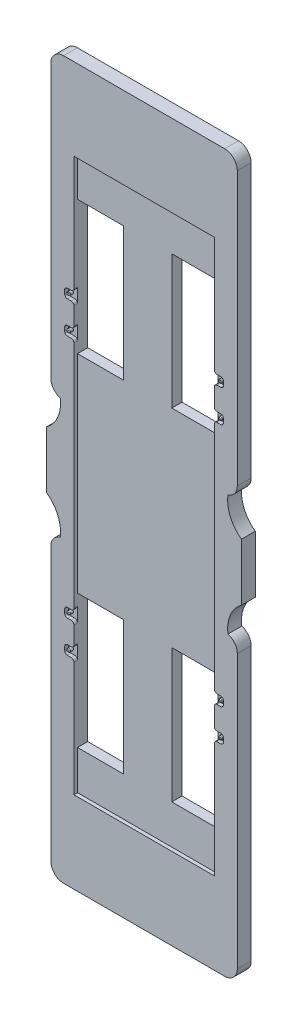
SolidWorks part; units mm, degrees
ref_plane "Front Plane" through (0, 0, 0) normal (0, 0, 1) x (1, 0, 0)
ref_plane "Top Plane" through (0, 0, 0) normal (0, 1, 0) x (1, 0, 0)
ref_plane "Right Plane" through (0, 0, 0) normal (1, 0, 0) x (0, 0, -1)
sketch "Sketch1" plane through (0, 0, 0.1) normal (0, 0, 1) x (1, 0, 0)
  line L12 (40.45, 31.4857) -> (40.45, 150)
  line L14 (40.45, 31.4857) -> (40.45, 150)
  line L16 (-40.45, -31.4857) -> (-40.45, -150)
  line L17 (-34.95, -155.5) -> (34.95, -155.5)
  line L18 (40.45, -150) -> (40.45, -31.4857)
  line L19 (42.25, -12.4178) -> (42.25, 12.4178)
  line L24 (-40.45, -31.4857) -> (-40.45, -150)
  line L25 (-34.95, -155.5) -> (34.95, -155.5)
  line L26 (40.45, -150) -> (40.45, -31.4857)
  line L27 (42.25, -12.4178) -> (42.25, 12.4178)
  line L38 (34.95, 155.5) -> (-34.95, 155.5)
  line L39 (34.95, 155.5) -> (-34.95, 155.5)
  line L40 (-40.45, 150) -> (-40.45, 31.4857)
  line L41 (-40.45, 150) -> (-40.45, 31.4857)
  line L42 (-42.25, 12.4178) -> (-42.25, -12.4178)
  line L43 (-42.25, 12.4178) -> (-42.25, -12.4178)
  line L48 (-30.45, 120) -> (-30.45, 70.2)
  line L49 (-31.65, 69) -> (-33.25, 69)
  line L50 (-34.45, 67.8) -> (-34.45, 66.2)
  line L51 (-33.25, 65) -> (-31.65, 65)
  line L52 (-30.45, 63.8) -> (-30.45, 56.2)
  line L53 (-31.65, 55) -> (-33.25, 55)
  line L54 (-34.45, 53.8) -> (-34.45, 52.2)
  line L55 (-33.25, 51) -> (-31.65, 51)
  line L56 (-30.45, 49.8) -> (-30.45, 0)
  line L57 (-30.45, 0) -> (30.45, 0)
  line L58 (30.45, 0) -> (30.45, 49.8)
  line L59 (31.65, 51) -> (33.25, 51)
  line L60 (34.45, 52.2) -> (34.45, 53.8)
  line L61 (33.25, 55) -> (31.65, 55)
  line L62 (30.45, 56.2) -> (30.45, 63.8)
  line L63 (31.65, 65) -> (33.25, 65)
  line L64 (34.45, 66.2) -> (34.45, 67.8)
  line L65 (33.25, 69) -> (31.65, 69)
  line L66 (30.45, 70.2) -> (30.45, 120)
  line L67 (30.45, 120) -> (-30.45, 120)
  line L68 (-30.45, 120) -> (-30.45, 70.2)
  line L69 (-31.65, 69) -> (-33.25, 69)
  line L70 (-34.45, 67.8) -> (-34.45, 66.2)
  line L71 (-33.25, 65) -> (-31.65, 65)
  line L72 (-30.45, 63.8) -> (-30.45, 56.2)
  line L73 (-31.65, 55) -> (-33.25, 55)
  line L74 (-34.45, 53.8) -> (-34.45, 52.2)
  line L75 (-33.25, 51) -> (-31.65, 51)
  line L76 (-30.45, 49.8) -> (-30.45, 0)
  line L77 (-30.45, 0) -> (30.45, 0)
  line L78 (30.45, 0) -> (30.45, 49.8)
  line L79 (31.65, 51) -> (33.25, 51)
  line L80 (34.45, 52.2) -> (34.45, 53.8)
  line L81 (33.25, 55) -> (31.65, 55)
  line L82 (30.45, 56.2) -> (30.45, 63.8)
  line L83 (31.65, 65) -> (33.25, 65)
  line L84 (34.45, 66.2) -> (34.45, 67.8)
  line L85 (33.25, 69) -> (31.65, 69)
  line L86 (30.45, 70.2) -> (30.45, 120)
  line L87 (30.45, 120) -> (-30.45, 120)
  line L88 (-30.45, 0) -> (-30.45, -49.8)
  line L89 (-31.65, -51) -> (-33.25, -51)
  line L90 (-34.45, -52.2) -> (-34.45, -53.8)
  line L91 (-33.25, -55) -> (-31.65, -55)
  line L92 (-30.45, -56.2) -> (-30.45, -63.8)
  line L93 (-31.65, -65) -> (-33.25, -65)
  line L94 (-34.45, -66.2) -> (-34.45, -67.8)
  line L95 (-33.25, -69) -> (-31.65, -69)
  line L96 (-30.45, -70.2) -> (-30.45, -120)
  line L97 (-30.45, -120) -> (30.45, -120)
  line L98 (30.45, -120) -> (30.45, -70.2)
  line L99 (31.65, -69) -> (33.25, -69)
  line L100 (34.45, -67.8) -> (34.45, -66.2)
  line L101 (33.25, -65) -> (31.65, -65)
  line L102 (30.45, -63.8) -> (30.45, -56.2)
  line L103 (31.65, -55) -> (33.25, -55)
  line L104 (34.45, -53.8) -> (34.45, -52.2)
  line L105 (33.25, -51) -> (31.65, -51)
  line L106 (30.45, -49.8) -> (30.45, 0)
  line L107 (30.45, 0) -> (-30.45, 0)
  line L108 (-30.45, 0) -> (-30.45, -49.8)
  line L109 (-31.65, -51) -> (-33.25, -51)
  line L110 (-34.45, -52.2) -> (-34.45, -53.8)
  line L111 (-33.25, -55) -> (-31.65, -55)
  line L112 (-30.45, -56.2) -> (-30.45, -63.8)
  line L113 (-31.65, -65) -> (-33.25, -65)
  line L114 (-34.45, -66.2) -> (-34.45, -67.8)
  line L115 (-33.25, -69) -> (-31.65, -69)
  line L116 (-30.45, -70.2) -> (-30.45, -120)
  line L117 (-30.45, -120) -> (30.45, -120)
  line L118 (30.45, -120) -> (30.45, -70.2)
  line L119 (31.65, -69) -> (33.25, -69)
  line L120 (34.45, -67.8) -> (34.45, -66.2)
  line L121 (33.25, -65) -> (31.65, -65)
  line L122 (30.45, -63.8) -> (30.45, -56.2)
  line L123 (31.65, -55) -> (33.25, -55)
  line L124 (34.45, -53.8) -> (34.45, -52.2)
  line L125 (33.25, -51) -> (31.65, -51)
  line L126 (30.45, -49.8) -> (30.45, 0)
  line L127 (30.45, 0) -> (-30.45, 0)
  circle A0 centre (-32.95, -67) radius 0.75 construction
  circle A1 centre (-32.95, -53) radius 0.75 construction
  circle A2 centre (32.95, -67) radius 0.75 construction
  circle A3 centre (32.95, -53) radius 0.75 construction
  circle A4 centre (32.95, 53) radius 0.75 construction
  circle A5 centre (32.95, 67) radius 0.75 construction
  circle A6 centre (-32.95, 53) radius 0.75 construction
  circle A7 centre (-32.95, 67) radius 0.75 construction
  circle A16 centre (-32.95, -67) radius 0.75
  circle A17 centre (-32.95, -53) radius 0.75
  circle A18 centre (32.95, -67) radius 0.75
  circle A19 centre (32.95, -53) radius 0.75
  circle A20 centre (32.95, 53) radius 0.75
  circle A21 centre (32.95, 67) radius 0.75
  circle A22 centre (-32.95, 53) radius 0.75
  circle A23 centre (-32.95, 67) radius 0.75
  arc A32 (-36.3903, -26.1776) -> (-42.25, -12.4178) centre (-50.75, -24.1652) ccw
  arc A33 (-36.3903, -26.1776) -> (-40.45, -31.4857) centre (-34.95, -31.4857) ccw
  arc A34 (-40.45, -150) -> (-34.95, -155.5) centre (-34.95, -150) ccw
  arc A35 (34.95, -155.5) -> (40.45, -150) centre (34.95, -150) ccw
  arc A36 (40.45, -31.4857) -> (36.3903, -26.1776) centre (34.95, -31.4857) ccw
  arc A37 (42.25, -12.4178) -> (36.3903, -26.1776) centre (50.75, -24.1652) ccw
  arc A44 (-36.3903, -26.1776) -> (-42.25, -12.4178) centre (-50.75, -24.1652) ccw
  arc A45 (-36.3903, -26.1776) -> (-40.45, -31.4857) centre (-34.95, -31.4857) ccw
  arc A46 (-40.45, -150) -> (-34.95, -155.5) centre (-34.95, -150) ccw
  arc A47 (34.95, -155.5) -> (40.45, -150) centre (34.95, -150) ccw
  arc A48 (40.45, -31.4857) -> (36.3903, -26.1776) centre (34.95, -31.4857) ccw
  arc A49 (42.25, -12.4178) -> (36.3903, -26.1776) centre (50.75, -24.1652) ccw
  arc A56 (-31.65, 69) -> (-30.45, 70.2) centre (-31.65, 70.2) ccw
  arc A57 (-33.25, 69) -> (-34.45, 67.8) centre (-33.25, 67.8) ccw
  arc A58 (-34.45, 66.2) -> (-33.25, 65) centre (-33.25, 66.2) ccw
  arc A59 (-30.45, 63.8) -> (-31.65, 65) centre (-31.65, 63.8) ccw
  arc A60 (-31.65, 55) -> (-30.45, 56.2) centre (-31.65, 56.2) ccw
  arc A61 (-33.25, 55) -> (-34.45, 53.8) centre (-33.25, 53.8) ccw
  arc A62 (-34.45, 52.2) -> (-33.25, 51) centre (-33.25, 52.2) ccw
  arc A63 (-30.45, 49.8) -> (-31.65, 51) centre (-31.65, 49.8) ccw
  arc A64 (31.65, 51) -> (30.45, 49.8) centre (31.65, 49.8) ccw
  arc A65 (33.25, 51) -> (34.45, 52.2) centre (33.25, 52.2) ccw
  arc A66 (34.45, 53.8) -> (33.25, 55) centre (33.25, 53.8) ccw
  arc A67 (30.45, 56.2) -> (31.65, 55) centre (31.65, 56.2) ccw
  arc A68 (31.65, 65) -> (30.45, 63.8) centre (31.65, 63.8) ccw
  arc A69 (33.25, 65) -> (34.45, 66.2) centre (33.25, 66.2) ccw
  arc A70 (34.45, 67.8) -> (33.25, 69) centre (33.25, 67.8) ccw
  arc A71 (30.45, 70.2) -> (31.65, 69) centre (31.65, 70.2) ccw
  arc A72 (-31.65, 69) -> (-30.45, 70.2) centre (-31.65, 70.2) ccw
  arc A73 (-33.25, 69) -> (-34.45, 67.8) centre (-33.25, 67.8) ccw
  arc A74 (-34.45, 66.2) -> (-33.25, 65) centre (-33.25, 66.2) ccw
  arc A75 (-30.45, 63.8) -> (-31.65, 65) centre (-31.65, 63.8) ccw
  arc A76 (-31.65, 55) -> (-30.45, 56.2) centre (-31.65, 56.2) ccw
  arc A77 (-33.25, 55) -> (-34.45, 53.8) centre (-33.25, 53.8) ccw
  arc A78 (-34.45, 52.2) -> (-33.25, 51) centre (-33.25, 52.2) ccw
  arc A79 (-30.45, 49.8) -> (-31.65, 51) centre (-31.65, 49.8) ccw
  arc A80 (31.65, 51) -> (30.45, 49.8) centre (31.65, 49.8) ccw
  arc A81 (33.25, 51) -> (34.45, 52.2) centre (33.25, 52.2) ccw
  arc A82 (34.45, 53.8) -> (33.25, 55) centre (33.25, 53.8) ccw
  arc A83 (30.45, 56.2) -> (31.65, 55) centre (31.65, 56.2) ccw
  arc A84 (31.65, 65) -> (30.45, 63.8) centre (31.65, 63.8) ccw
  arc A85 (33.25, 65) -> (34.45, 66.2) centre (33.25, 66.2) ccw
  arc A86 (34.45, 67.8) -> (33.25, 69) centre (33.25, 67.8) ccw
  arc A87 (30.45, 70.2) -> (31.65, 69) centre (31.65, 70.2) ccw
  arc A100 (-31.65, -51) -> (-30.45, -49.8) centre (-31.65, -49.8) ccw
  arc A101 (-33.25, -51) -> (-34.45, -52.2) centre (-33.25, -52.2) ccw
  arc A102 (-34.45, -53.8) -> (-33.25, -55) centre (-33.25, -53.8) ccw
  arc A103 (-30.45, -56.2) -> (-31.65, -55) centre (-31.65, -56.2) ccw
  arc A104 (-31.65, -65) -> (-30.45, -63.8) centre (-31.65, -63.8) ccw
  arc A105 (-33.25, -65) -> (-34.45, -66.2) centre (-33.25, -66.2) ccw
  arc A106 (-34.45, -67.8) -> (-33.25, -69) centre (-33.25, -67.8) ccw
  arc A107 (-30.45, -70.2) -> (-31.65, -69) centre (-31.65, -70.2) ccw
  arc A108 (31.65, -69) -> (30.45, -70.2) centre (31.65, -70.2) ccw
  arc A109 (33.25, -69) -> (34.45, -67.8) centre (33.25, -67.8) ccw
  arc A110 (34.45, -66.2) -> (33.25, -65) centre (33.25, -66.2) ccw
  arc A111 (30.45, -63.8) -> (31.65, -65) centre (31.65, -63.8) ccw
  arc A112 (31.65, -55) -> (30.45, -56.2) centre (31.65, -56.2) ccw
  arc A113 (33.25, -55) -> (34.45, -53.8) centre (33.25, -53.8) ccw
  arc A114 (34.45, -52.2) -> (33.25, -51) centre (33.25, -52.2) ccw
  arc A115 (30.45, -49.8) -> (31.65, -51) centre (31.65, -49.8) ccw
  arc A116 (-31.65, -51) -> (-30.45, -49.8) centre (-31.65, -49.8) ccw
  arc A117 (-33.25, -51) -> (-34.45, -52.2) centre (-33.25, -52.2) ccw
  arc A118 (-34.45, -53.8) -> (-33.25, -55) centre (-33.25, -53.8) ccw
  arc A119 (-30.45, -56.2) -> (-31.65, -55) centre (-31.65, -56.2) ccw
  arc A120 (-31.65, -65) -> (-30.45, -63.8) centre (-31.65, -63.8) ccw
  arc A121 (-33.25, -65) -> (-34.45, -66.2) centre (-33.25, -66.2) ccw
  arc A122 (-34.45, -67.8) -> (-33.25, -69) centre (-33.25, -67.8) ccw
  arc A123 (-30.45, -70.2) -> (-31.65, -69) centre (-31.65, -70.2) ccw
  arc A124 (31.65, -69) -> (30.45, -70.2) centre (31.65, -70.2) ccw
  arc A125 (33.25, -69) -> (34.45, -67.8) centre (33.25, -67.8) ccw
  arc A126 (34.45, -66.2) -> (33.25, -65) centre (33.25, -66.2) ccw
  arc A127 (30.45, -63.8) -> (31.65, -65) centre (31.65, -63.8) ccw
  arc A128 (31.65, -55) -> (30.45, -56.2) centre (31.65, -56.2) ccw
  arc A129 (33.25, -55) -> (34.45, -53.8) centre (33.25, -53.8) ccw
  arc A130 (34.45, -52.2) -> (33.25, -51) centre (33.25, -52.2) ccw
  arc A131 (30.45, -49.8) -> (31.65, -51) centre (31.65, -49.8) ccw
  arc A138 (36.3903, 26.1776) -> (42.25, 12.4178) centre (50.75, 24.1652) ccw
  arc A139 (36.3903, 26.1776) -> (42.25, 12.4178) centre (50.75, 24.1652) ccw
  arc A140 (36.3903, 26.1776) -> (40.45, 31.4857) centre (34.95, 31.4857) ccw
  arc A141 (36.3903, 26.1776) -> (40.45, 31.4857) centre (34.95, 31.4857) ccw
  arc A142 (40.45, 150) -> (34.95, 155.5) centre (34.95, 150) ccw
  arc A143 (40.45, 150) -> (34.95, 155.5) centre (34.95, 150) ccw
  arc A144 (-34.95, 155.5) -> (-40.45, 150) centre (-34.95, 150) ccw
  arc A145 (-34.95, 155.5) -> (-40.45, 150) centre (-34.95, 150) ccw
  arc A146 (-40.45, 31.4857) -> (-36.3903, 26.1776) centre (-34.95, 31.4857) ccw
  arc A147 (-40.45, 31.4857) -> (-36.3903, 26.1776) centre (-34.95, 31.4857) ccw
  arc A148 (-42.25, 12.4178) -> (-36.3903, 26.1776) centre (-50.75, 24.1652) ccw
  arc A149 (-42.25, 12.4178) -> (-36.3903, 26.1776) centre (-50.75, 24.1652) ccw
  line M21 (10.45, -103) -> (10.45, -45)
  line M22 (10.45, -45) -> (30.45, -45)
  line M23 (30.45, -45) -> (30.45, -103)
  line M24 (30.45, -103) -> (10.45, -103)
  line M25 (-10.45, -103) -> (-30.45, -103)
  line M26 (-30.45, -103) -> (-30.45, -45)
  line M27 (-30.45, -45) -> (-10.45, -45)
  line M28 (-10.45, -45) -> (-10.45, -103)
  line M29 (-10.45, 103) -> (-10.45, 45)
  line M30 (-10.45, 45) -> (-30.45, 45)
  line M31 (-30.45, 45) -> (-30.45, 103)
  line M32 (-30.45, 103) -> (-10.45, 103)
  line M33 (10.45, 103) -> (30.45, 103)
  line M34 (30.45, 103) -> (30.45, 45)
  line M35 (30.45, 45) -> (10.45, 45)
  line M36 (10.45, 45) -> (10.45, 103)
  dimension "D2" = 0
  dimension "D3" = 0
  dimension "D1" = 5
extrude "Boss-Extrude1" add sketch "Sketch1" along normal up to surface (4.43 mm away) contours A149 L43 A44 A45 L24 A46 L25 A47 L26 A48 A49 L27 A139 A141 L14 A143 L39 A145 L41 A147 A131 L125 A130 L124 A129 L123 A128 A127 L121 A126 L120 A125 L119 A124 L118 L117 L116 A123 L115 A122 L114 A121 L113 A120 A119 M23 M26 | L126 L77 L108 L116 L117 L118 M22 M27 M28 M25 M24 M21 | A119 A116 L109 A117 L110 A118 L111 A17 M26 | A17 | A123 A120 L113 A121 L114 A122 L115 A16 M26 | A16 | A18 | A127 A124 L119 A125 L120 A126 L121 A18 M23 | A131 A128 L123 A129 L124 A130 L125 A19 M23 | A19 | L86 L87 L68 L76 L77 L78 M32 M29 M30 M35 M36 M33 | A75 A72 L69 A73 L70 A74 L71 A23 M31 | A23 | A79 A76 L73 A77 L74 A78 L75 A22 M31 | A22 | A87 A84 L83 A85 L84 A86 L85 A21 M34 | A21 | A83 A80 L79 A81 L80 A82 L81 A20 M34 | A20 region at (36.7589, 30.1022, 0.1) region at (0, 53.4884, 0.1) region at (-30.5255, 67, 0.1) region at (30.7481, 69.2981, 0.1) region at (-30.5255, 53, 0.1) region at (0, -53.4884, 0.1) region at (30.7481, 55.2981, 0.1) region at (-30.5255, -53, 0.1) region at (30.7481, -50.7019, 0.1) region at (-30.5255, -67, 0.1) region at (30.7481, -64.7019, 0.1) region at (-32.95, -67, 0.1) region at (-32.95, -53, 0.1) region at (32.95, -67, 0.1) region at (32.95, -53, 0.1) region at (32.95, 53, 0.1) region at (32.95, 67, 0.1) region at (-32.95, 53, 0.1) region at (-32.95, 67, 0.1)
extrude "Boss-Extrude2" add sketch "Sketch1<3>" along normal up to surface (6 mm away) contours A149 L43 A44 A45 L24 A46 L25 A47 L26 A48 A49 L27 A139 A141 L14 A143 L39 A145 L41 A147 A131 L125 A130 L124 A129 L123 A128 A127 L121 A126 L120 A125 L119 A124 L118 L117 L116 A123 L115 A122 L114 A121 L113 A120 A119 M23 M26 | A23 | A22 | A21 | A20 | A17 | A16 | A19 | A18 region at (36.7589, 30.1022, 0.1) region at (-32.95, -67, 0.1) region at (-32.95, -53, 0.1) region at (32.95, -67, 0.1) region at (32.95, -53, 0.1) region at (32.95, 53, 0.1) region at (32.95, 67, 0.1) region at (-32.95, 53, 0.1) region at (-32.95, 67, 0.1)
sketch "Sketch1<3>" plane through (0, 0, 0.1) normal (0, 0, 1) x (1, 0, 0) same geometry as "Sketch1"
fillet "Fillet1" radius 0.3 8 edges at (-33.7, -67, 6.1) (-33.7, -53, 6.1) (32.2, -67, 6.1) (32.2, -53, 6.1) (32.2, 53, 6.1) (32.2, 67, 6.1) (-33.7, 53, 6.1) (-33.7, 67, 6.1)
sketch "Sketch2" plane through (0, 0, -4.9) normal (0, 0, -1) x (-1, 0, 0)
  line L11 (-42.25, 0) -> (-28.1667, 0)
  line L22 (-42.25, -12.4178) -> (-42.25, 12.4178) construction
  line L24 (-28.1667, 0) -> (-33.1667, 5)
  line L25 (-33.1667, 5) -> (-9.0833, 5)
  line L26 (-9.0833, 5) -> (-14.0833, 0)
  line L27 (51.95, 0) -> (-51.95, 0) construction
  line L28 (-14.0833, 0) -> (0, 0)
  line L29 (-54.525, 5) -> (-79.675, 5) construction
  line L30 (-28.1667, 0) -> (-14.0833, 0) construction
  line L31 (0, 0) -> (14.0833, 0)
  line L32 (0, 0) -> (0, 23.8977) construction
  line L34 (28.1667, 0) -> (14.0833, 0) construction
  line L35 (9.0833, 5) -> (14.0833, 0)
  line L36 (33.1667, 5) -> (9.0833, 5)
  line L37 (28.1667, 0) -> (33.1667, 5)
  line L38 (42.25, 0) -> (28.1667, 0)
  point P19 (0, 0)
  dimension "D1" = 45
